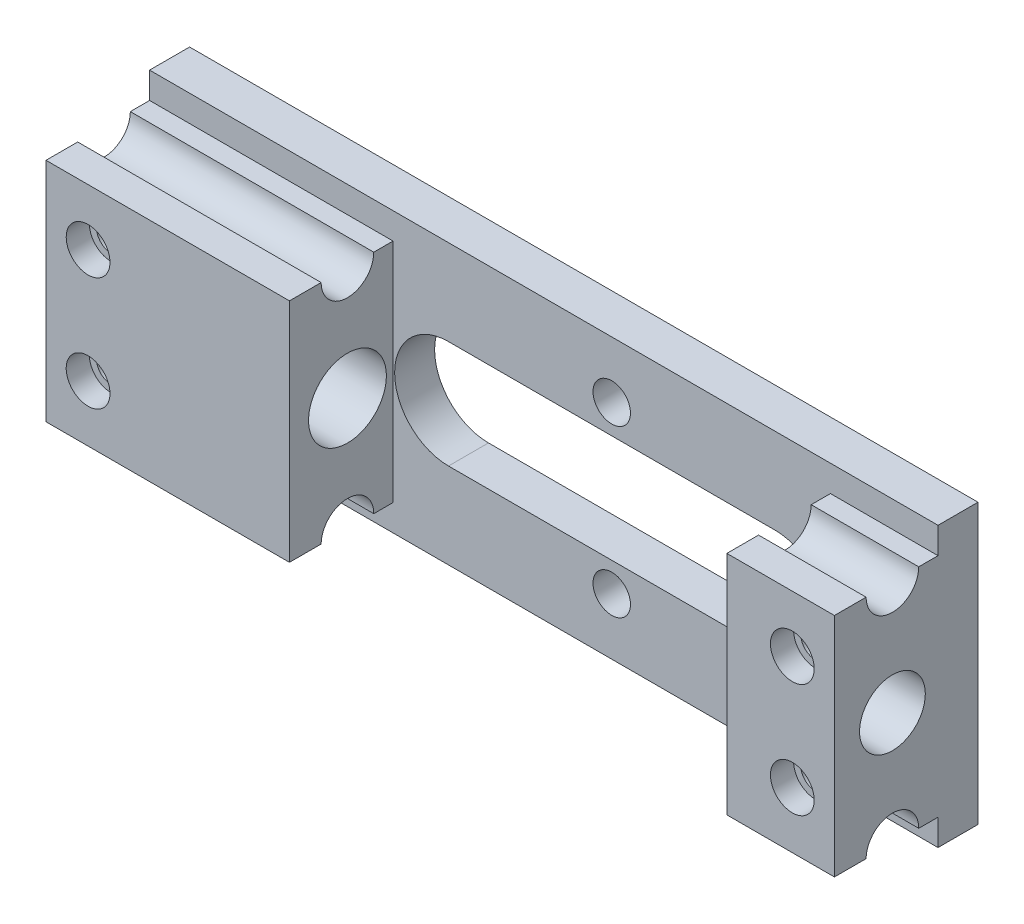
SolidWorks part; units mm, degrees
ref_plane "Front Plane" through (0, 0, 0) normal (0, 0, 1) x (1, 0, 0)
ref_plane "Top Plane" through (0, 0, 0) normal (0, 1, 0) x (1, 0, 0)
ref_plane "Right Plane" through (0, 0, 0) normal (1, 0, 0) x (0, 0, -1)
sketch "Sketch1" plane through (0, 0, 0) normal (0, 0, 1) x (1, 0, 0)
  line L1 (-22.0345, -8.4201) -> (22.0345, -8.4201)
  line L2 (-22.0345, -8.4201) -> (-22.0345, 8.4201)
  line L3 (-22.0345, 8.4201) -> (22.0345, 8.4201)
  line L4 (22.0345, -8.4201) -> (22.0345, 8.4201)
  line L5 (-22.0345, -8.4201) -> (22.0345, 8.4201) construction
  line L6 (-22.0345, 8.4201) -> (22.0345, -8.4201) construction
  point P0 (0, 0)
  dimension "D1" = 44.069
  dimension "D2" = 16.8402
extrude "Boss-Extrude1" add sketch "Sketch1" along normal blind 7.1628
sketch "Sketch2" plane through (0, 0, 7.1628) normal (0, 0, 1) x (1, 0, 0)
  line L0 (-22.0345, 0) -> (22.0345, 0) construction
  line L1 (-10.8458, 8.4201) -> (15.5448, 8.4201)
  line L2 (-10.8458, 8.4201) -> (-10.8458, -8.4201)
  line L3 (-10.8458, -8.4201) -> (15.5448, -8.4201)
  line L4 (15.5448, 8.4201) -> (15.5448, -8.4201)
  line L5 (-22.0345, 8.4201) -> (-22.0345, -8.4201) construction
  line L6 (22.0345, -8.4201) -> (22.0345, 8.4201) construction
  line L7 (-10.8458, 8.4201) -> (-22.0345, 0) construction
  line L8 (-22.0345, 0) -> (-10.8458, -8.4201) construction
  line L9 (2.3495, 8.4201) -> (2.3495, -8.4201) construction
  line L12 (22.0345, 8.4201) -> (-22.0345, 8.4201) construction
  dimension "D1" = 26.3906
  dimension "D2" = 24.384
extrude "Cut-Extrude1" cut sketch "Sketch2" against normal blind 4.75
sketch "Sketch4" plane through (0, 0, 7.1628) normal (0, 0, 1) x (1, 0, 0)
  line L0 (-10.8458, 8.4201) -> (-10.8458, -8.4201) construction
  line L1 (-22.0345, -8.4201) -> (-10.8458, -8.4201)
  line L2 (-22.0345, -8.4201) -> (-22.0345, -6.8326)
  line L3 (-22.0345, -6.8326) -> (-10.8458, -6.8326)
  line L4 (-10.8458, -8.4201) -> (-10.8458, -6.8326)
  line L5 (-22.0345, 0) -> (-10.8458, 0) construction
  line L6 (-22.0345, 8.4201) -> (-22.0345, -8.4201) construction
  line L7 (-10.8458, 8.4201) -> (-10.8458, -8.4201) construction
  line L8 (-10.8458, 8.4201) -> (-10.8458, 6.8326)
  line L9 (-22.0345, 6.8326) -> (-10.8458, 6.8326)
  line L10 (-22.0345, 8.4201) -> (-22.0345, 6.8326)
  line L11 (-22.0345, 8.4201) -> (-10.8458, 8.4201)
  line L12 (22.0345, -8.4201) -> (22.0345, 8.4201) construction
  line L13 (15.5448, -8.4201) -> (22.0345, -8.4201)
  line L14 (15.5448, -8.4201) -> (15.5448, -6.8326)
  line L15 (15.5448, -6.8326) -> (22.0345, -6.8326)
  line L16 (22.0345, -8.4201) -> (22.0345, -6.8326)
  line L17 (15.5448, 6.8326) -> (22.0345, 6.8326)
  line L18 (22.0345, 8.4201) -> (22.0345, 6.8326)
  line L19 (15.5448, 8.4201) -> (22.0345, 8.4201)
  line L20 (15.5448, 8.4201) -> (15.5448, 6.8326)
  dimension "D1" = 1.5875
extrude "Cut-Extrude9" cut sketch "Sketch4" against normal up to surface (4.75 mm away) up to face at (2.3495, 0, 2.4128)
sketch "Sketch5" plane through (-22.0345, 0, 0) normal (-1, 0, 0) x (0, 0, 1)
  line L1 (0, 0) -> (7.1628, 0) construction
  line L2 (0, 8.4201) -> (0, -8.4201) construction
  line L3 (7.1628, 6.8326) -> (7.1628, -6.8326) construction
  circle A0 centre (5.1628, -6.8326) radius 1.5875
  circle A1 centre (5.1628, 6.8326) radius 1.5875
  dimension "D1" = 3.175
  dimension "D2" = 2
extrude "Cut-Extrude10" cut sketch "Sketch5" against normal through all
sketch "Sketch14" plane through (0, 0, 7.1628) normal (0, 0, 1) x (1, 0, 0)
  line L4 (-10.8458, -6.8326) -> (-10.8458, 6.8326)
  line L5 (-10.8458, 6.8326) -> (-22.0345, 6.8326)
  line L6 (-22.0345, 6.8326) -> (-22.0345, -6.8326)
  line L7 (-22.0345, -6.8326) -> (-10.8458, -6.8326)
  line L8 (-10.8458, -6.8326) -> (-10.8458, 6.8326)
  line L9 (-10.8458, 6.8326) -> (-22.0345, 6.8326)
  line L10 (-22.0345, 6.8326) -> (-22.0345, -6.8326)
  line L11 (-22.0345, -6.8326) -> (-10.8458, -6.8326)
  line L12 (22.0345, -6.8326) -> (22.0345, 6.8326)
  line L13 (22.0345, 6.8326) -> (15.5448, 6.8326)
  line L14 (15.5448, 6.8326) -> (15.5448, -6.8326)
  line L15 (15.5448, -6.8326) -> (22.0345, -6.8326)
  line L16 (22.0345, -6.8326) -> (22.0345, 6.8326)
  line L17 (22.0345, 6.8326) -> (15.5448, 6.8326)
  line L18 (15.5448, 6.8326) -> (15.5448, -6.8326)
  line L19 (15.5448, -6.8326) -> (22.0345, -6.8326)
  dimension "D1" = 0
  dimension "D2" = 0
extrude "Boss-Extrude3" add sketch "Sketch14" along normal blind 1.5
sketch "Sketch6" plane through (0, 0, 8.6628) normal (0, 0, 1) x (1, 0, 0)
  line L0 (-22.0345, 0) -> (-10.8458, 0) construction
  line L2 (-10.8458, 6.8326) -> (-10.8458, -6.8326) construction
  line L3 (-22.0345, 6.8326) -> (-22.0345, -6.8326) construction
  circle A0 centre (-14.7955, 3.429) radius 0.889
  circle A1 centre (-14.7955, -3.429) radius 0.889
  circle A2 centre (19.4945, 3.429) radius 0.889
  circle A3 centre (19.4945, -3.429) radius 0.889
  dimension "D1" = 1.778
  dimension "D2" = 6.858
  dimension "D3" = 7.239
  dimension "D4" = 2
extrude "Cut-Extrude11" cut sketch "Sketch6" against normal through all contours A2 | A3 region at (19.4945, 3.429, 8.6628) region at (19.4945, -3.429, 8.6628)
sketch "Sketch7" plane through (0, 0, 8.6628) normal (0, 0, 1) x (1, 0, 0)
  circle A2 centre (19.4945, 3.429) radius 1.3208
  circle A3 centre (19.4945, -3.429) radius 1.3208
extrude "Cut-Extrude12" cut sketch "Sketch7" against normal blind 1.397
sketch "Sketch9" plane through (0, 0, 0) normal (0, 0, -1) x (-1, 0, 0)
  line L0 (22.0345, 8.4201) -> (22.0345, -8.4201) construction
  line L1 (-22.0345, 0) -> (22.0345, 0) construction
  line L2 (-22.0345, -8.4201) -> (-22.0345, 8.4201) construction
  circle A0 centre (-2.3495, 5) radius 1.1303
  circle A1 centre (-2.3495, -5) radius 1.1303
  dimension "D1" = 2.2606
  dimension "D2" = 24.384
  dimension "D3" = 10
extrude "Cut-Extrude13" cut sketch "Sketch9" against normal through all
sketch "Sketch11" plane through (0, 0, 0) normal (0, 0, -1) x (-1, 0, 0)
  line L0 (-22.0345, 0) -> (22.0345, 0) construction
  line L1 (-22.0345, -8.4201) -> (-22.0345, 8.4201) construction
  line L2 (22.0345, 8.4201) -> (22.0345, -8.4201) construction
  line L3 (-2.3495, 5) -> (-2.3495, -5) construction
  line L4 (-12.1995, 0) -> (7.5005, 0) construction
  line L5 (-12.1995, 3.25) -> (7.5005, 3.25)
  line L6 (-12.1995, -3.25) -> (7.5005, -3.25)
  arc A0 (-12.1995, 3.25) -> (-12.1995, -3.25) centre (-12.1995, 0) ccw
  arc A1 (7.5005, -3.25) -> (7.5005, 3.25) centre (7.5005, 0) ccw
  circle A2 centre (-2.3495, -5) radius 1.1303 construction
  point P12 (-2.3495, 0)
  dimension "D1" = 6.5
  dimension "D2" = 19.7
extrude "Cut-Extrude15" cut sketch "Sketch11" against normal through all
sketch "Sketch12" plane through (-10.8458, 0, 0) normal (1, 0, 0) x (0, 0, -1)
  circle A0 centre (-5.1628, 0) radius 2.3495
  dimension "D1" = 4.699
extrude "Cut-Extrude16" cut sketch "Sketch12" against normal blind 10.922
sketch "Sketch15" plane through (-22.0345, 0, 0) normal (-1, 0, 0) x (0, 0, 1)
  line L10 (8.6628, 6.8326) -> (6.7503, 6.8326)
  line L11 (3.5753, 6.8326) -> (2.4128, 6.8326)
  line L12 (2.4128, 6.8326) -> (2.4128, 8.4201)
  line L13 (2.4128, 8.4201) -> (0, 8.4201)
  line L14 (0, 8.4201) -> (0, -8.4201)
  line L15 (0, -8.4201) -> (2.4128, -8.4201)
  line L16 (2.4128, -8.4201) -> (2.4128, -6.8326)
  line L17 (2.4128, -6.8326) -> (3.5753, -6.8326)
  line L18 (6.7503, -6.8326) -> (8.6628, -6.8326)
  line L19 (8.6628, -6.8326) -> (8.6628, 6.8326)
  line L20 (8.6628, 6.8326) -> (6.7503, 6.8326)
  line L21 (3.5753, 6.8326) -> (2.4128, 6.8326)
  line L22 (2.4128, 6.8326) -> (2.4128, 8.4201)
  line L23 (2.4128, 8.4201) -> (0, 8.4201)
  line L24 (0, 8.4201) -> (0, -8.4201)
  line L25 (0, -8.4201) -> (2.4128, -8.4201)
  line L26 (2.4128, -8.4201) -> (2.4128, -6.8326)
  line L27 (2.4128, -6.8326) -> (3.5753, -6.8326)
  line L28 (6.7503, -6.8326) -> (8.6628, -6.8326)
  line L29 (8.6628, -6.8326) -> (8.6628, 6.8326)
  arc A2 (3.5753, 6.8326) -> (6.7503, 6.8326) centre (5.1628, 6.8326) ccw
  arc A3 (6.7503, -6.8326) -> (3.5753, -6.8326) centre (5.1628, -6.8326) ccw
  arc A4 (3.5753, 6.8326) -> (6.7503, 6.8326) centre (5.1628, 6.8326) ccw
  arc A5 (6.7503, -6.8326) -> (3.5753, -6.8326) centre (5.1628, -6.8326) ccw
  dimension "D1" = 0
extrude "Boss-Extrude4" add sketch "Sketch15" along normal blind 3.5
ref_plane "Plane1" through (-1.75, 0, 0) normal (1, 0, 0) x (0, 0, -1)
mirror "Mirror1" about plane through (-1.75, 0, 0) normal (1, 0, 0) of "Cut-Extrude11", "Cut-Extrude12"
sketch "Sketch16" plane through (22.0345, 0, 0) normal (1, 0, 0) x (0, 0, -1)
  circle A0 centre (-5.1628, 0) radius 1.9844
  dimension "D1" = 3.9688
extrude "Cut-Extrude17" cut sketch "Sketch16" against normal up to next
